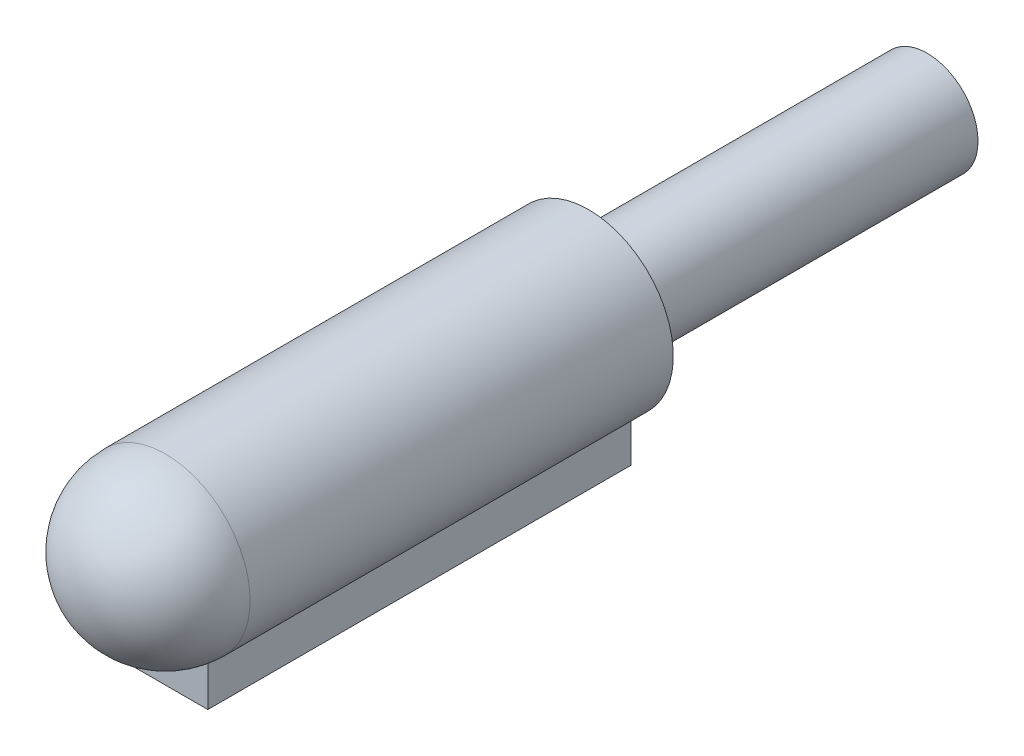
SolidWorks part; units mm, degrees
ref_plane "Płaszczyzna przednia" through (0, 0, 0) normal (0, 0, 1) x (1, 0, 0)
ref_plane "Płaszczyzna górna" through (0, 0, 0) normal (0, 1, 0) x (1, 0, 0)
ref_plane "Płaszczyzna prawa" through (0, 0, 0) normal (1, 0, 0) x (0, 0, -1)
sketch "Szkic1" plane through (0, 0, 0) normal (0, 0, 1) x (1, 0, 0)
  circle A0 centre (0, 0) radius 5
  circle A1 centre (0, 0) radius 3
  dimension "D1" = 10
  dimension "D2" = 2
extrude "Dodanie-wyciągnięcie1" add sketch "Szkic1" along normal blind 30 contours A0 A1 | A1 region at (-4.8586, 0, 0)
extrude "Dodanie-wyciągnięcie2" add sketch "Szkic1<3>" against normal blind 20 contours A1 region at (0, 0, 0)
sketch "Szkic1<3>" plane through (0, 0, 0) normal (0, 0, 1) x (1, 0, 0) same geometry as "Szkic1"
fillet "Zaokrąglenie1" radius 5 1 edges at (5, 0, 30)
sketch "Szkic3" plane through (0, 0, 0) normal (0, 0, -1) x (-1, 0, 0)
  line L0 (2.5, -4.3301) -> (2.5, -6.8301)
  line L1 (2.5, -6.8301) -> (-2.5, -6.8301)
  line L2 (-2.5, -6.8301) -> (-2.5, -4.3301)
  circle A0 centre (0, 0) radius 5 construction
  circle A1 centre (0, 0) radius 5
  circle M5 centre (0, 0) radius 5
  dimension "D1" = 2.5
  dimension "D2" = 5
  dimension "D3" = 2.5
  dimension "D4" = 90
extrude "Dodanie-wyciągnięcie3" add sketch "Szkic3" against normal blind 25 contours L2 L1 L0 M5 region at (0, -5.7971, 0)
